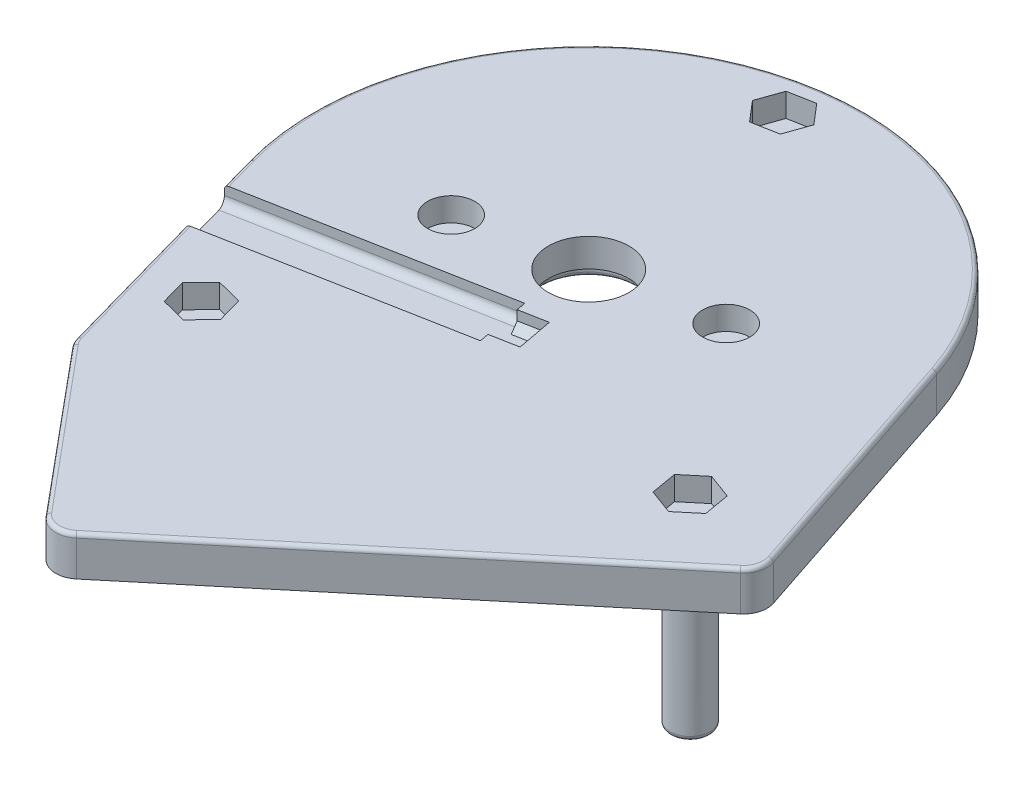
SolidWorks part; units mm, degrees
ref_plane "Front Plane" through (0, 0, 0) normal (0, 0, 1) x (1, 0, 0)
ref_plane "Top Plane" through (0, 0, 0) normal (0, 1, 0) x (1, 0, 0)
ref_plane "Right Plane" through (0, 0, 0) normal (1, 0, 0) x (0, 0, -1)
ref_plane "Plane1" through (0, 26, 0) normal (0, 1, 0) x (1, 0, 0)
sketch "Sketch1" plane through (0, 26, 0) normal (0, 1, 0) x (1, 0, 0)
  line L1 (-17.8615, -28.9506) -> (-18.7668, -25.7267)
  line L2 (-18.7668, -25.7267) -> (-22.0115, -24.8987)
  line L3 (-22.0115, -24.8987) -> (-24.3508, -27.2947)
  line L4 (-3.463, -61.6805) -> (42.6058, -23.3107)
  line L5 (43.5332, -20.0607) -> (33.2189, 11.0229)
  line L6 (-33.6967, -9.4621) -> (-25.1407, -39.932)
  line L7 (-24.5576, -41.0409) -> (-7.6881, -61.2953)
  line L8 (-3.463, -61.6805) -> (42.6058, -23.3107)
  line L9 (43.5332, -20.0607) -> (33.2189, 11.0229)
  line L10 (-33.6967, -9.4621) -> (-25.1407, -39.932)
  line L11 (-24.5576, -41.0409) -> (-7.6881, -61.2953)
  line L12 (-24.3508, -27.2947) -> (-23.4456, -30.5186)
  line L13 (-23.4456, -30.5186) -> (-20.2009, -31.3466)
  line L14 (-20.2009, -31.3466) -> (-17.8615, -28.9506)
  line L15 (31.7653, -21.5974) -> (34.3383, -19.4543)
  line L16 (34.3383, -19.4543) -> (33.7689, -16.1544)
  line L17 (33.7689, -16.1544) -> (30.6264, -14.9976)
  line L18 (30.6264, -14.9976) -> (28.0534, -17.1407)
  line L19 (28.0534, -17.1407) -> (28.6228, -20.4405)
  line L20 (28.6228, -20.4405) -> (31.7653, -21.5974)
  line L28 (0, 0) -> (-14.7176, -2.7648) construction
  line L29 (-0.9153, 4.8725) -> (0.9153, -4.8725) construction
  line L30 (-21.1062, -28.1227) -> (31.1959, -18.2975) construction
  line L52 (-7.0569, 32.1421) -> (-8.167, 28.9829)
  line L53 (-8.167, 28.9829) -> (-5.9861, 26.4418)
  line L54 (-5.9861, 26.4418) -> (-2.695, 27.0601)
  line L55 (-2.695, 27.0601) -> (-1.5849, 30.2193)
  line L56 (-1.5849, 30.2193) -> (-3.7659, 32.7604)
  line L57 (-3.7659, 32.7604) -> (-7.0569, 32.1421)
  circle A0 centre (0, 0) radius 5.125 construction
  circle A1 centre (0, 0) radius 5.125 construction
  circle A2 centre (31.1959, -18.2975) radius 3 construction
  circle A3 centre (-21.1062, -28.1227) radius 3 construction
  arc A4 (42.6058, -23.3107) -> (43.5332, -20.0607) centre (40.6859, -21.0055) ccw
  arc A5 (33.2189, 11.0229) -> (-33.6967, -9.4621) centre (0, 0) ccw
  arc A6 (-25.1407, -39.932) -> (-24.5576, -41.0409) centre (-22.2524, -39.121) ccw
  arc A7 (-7.6881, -61.2953) -> (-3.463, -61.6805) centre (-5.3829, -59.3754) ccw
  arc A8 (42.6058, -23.3107) -> (43.5332, -20.0607) centre (40.6859, -21.0055) ccw
  arc A9 (33.2189, 11.0229) -> (-33.6967, -9.4621) centre (0, 0) ccw
  arc A10 (-25.1407, -39.932) -> (-24.5576, -41.0409) centre (-22.2524, -39.121) ccw
  arc A11 (-7.6881, -61.2953) -> (-3.463, -61.6805) centre (-5.3829, -59.3754) ccw
  circle A12 centre (31.1959, -18.2975) radius 3 construction
  circle A13 centre (-21.1062, -28.1227) radius 3 construction
  circle A14 centre (0, 0) radius 5.125
  circle A15 centre (0, 0) radius 5.925
  circle A16 centre (31.1959, -18.2975) radius 1.6
  circle A17 centre (-21.1062, -28.1227) radius 1.6
  circle A18 centre (-21.1062, -28.1227) radius 2.9 construction
  circle A19 centre (31.1959, -18.2975) radius 2.9 construction
  circle A20 centre (-21.1062, -28.1227) radius 1.75
  circle A21 centre (-21.1062, -28.1227) radius 2.55
  circle A22 centre (31.1959, -18.2975) radius 1.75
  circle A23 centre (31.1959, -18.2975) radius 2.55
  circle A29 centre (-14.7176, -2.7648) radius 1.6
  circle A30 centre (-14.7176, -2.7648) radius 3
  circle A31 centre (14.7176, 2.7648) radius 1.6
  circle A32 centre (14.7176, 2.7648) radius 3
  circle A57 centre (-4.876, 29.6011) radius 1.6 construction
  circle A58 centre (-4.876, 29.6011) radius 1.6 construction
  circle A59 centre (-4.876, 29.6011) radius 1.6
  circle A60 centre (-4.876, 29.6011) radius 1.75
  circle A61 centre (-4.876, 29.6011) radius 2.55
  circle A62 centre (-4.876, 29.6011) radius 2.9 construction
  point P44 (0, 0)
  dimension "D2" = 10.25
  dimension "D3" = 11.85
  dimension "D4" = 3.2
  dimension "D6" = 3.2
  dimension "D8" = 3.2
  dimension "D9" = 6
  dimension "D11" = 3.5
  dimension "D13" = 3.5
  dimension "D15" = 3.2
  dimension "D16" = 3.5
  dimension "D5" = 5.8
  dimension "D7" = 5.8
  dimension "D10" = 29.95
  dimension "D12" = 0.8
  dimension "D14" = 0.8
  dimension "D17" = 0.8
  dimension "D18" = 5.8
  dimension "D1" = 0
extrude "Boss-Extrude7" add sketch "Sketch1" along normal blind 5 contours L11 A11 L8 A8 L9 A9 L10 A10 A30 A15 L14 L13 L12 L3 L2 L1 L20 L19 L18 L17 L16 L15 L57 L56 L55 L54 L53 L52 A32 | A30 A29 | A32 A31 | A15 A14 | L13 L14 L1 L2 L3 L12 A21 | A21 A20 | A20 A17 | L19 L20 L15 L16 L17 L18 A23 | A23 A22 | A22 A16 | L56 L57 L52 L53 L54 L55 A61 | A61 A60 | A60 A59 region at (-19.0967, 26, 30.0847) region at (1.6104, 26, 9.9024) region at (30.2255, 26, 20.9334) region at (-5.3945, 26, -32.3616) region at (-5.7574, 26, 0) region at (-22.8067, 26, 28.1227) region at (-23.5841, 26, 28.1227) region at (29.4954, 26, 18.2975) region at (28.718, 26, 18.2975) region at (-17.6327, 26, 2.7648) region at (11.8024, 26, -2.7648) region at (-6.5765, 26, -29.6011) region at (-7.3538, 26, -29.6011)
extrude "Cut-Extrude5" cut sketch "Sketch1<10>" against normal blind 3 from surface contours A30 A29 | A32 A31 | L19 L20 L15 L16 L17 L18 A23 | A23 A22 | A22 A16 | L13 L14 L1 L2 L3 L12 A21 | A21 A20 | A20 A17 | L56 L57 L52 L53 L54 L55 A61 | A61 A60 | A60 A59 region at (-19.0967, 26, 30.0847) region at (30.2255, 26, 20.9334) region at (-5.3945, 26, -32.3616) region at (-22.8067, 26, 28.1227) region at (-23.5841, 26, 28.1227) region at (29.4954, 26, 18.2975) region at (28.718, 26, 18.2975) region at (-17.6327, 26, 2.7648) region at (11.8024, 26, -2.7648) region at (-6.5765, 26, -29.6011) region at (-7.3538, 26, -29.6011) starting at face at (1.8961, 31, 26.7652)
sketch "Sketch1<10>" plane through (0, 26, 0) normal (0, 1, 0) x (1, 0, 0) same geometry as "Sketch1"
extrude "Boss-Extrude8" add sketch "Sketch1<11>" against normal blind 0.2 from surface contours A16 | A17 | A29 | A31 | A59 region at (31.1959, 26, 18.2975) region at (-21.1062, 26, 28.1227) region at (-14.7176, 26, 2.7648) region at (14.7176, 26, -2.7648) region at (-4.876, 26, -29.6011) starting at face at (-14.7176, 28, 4.3648)
sketch "Sketch1<11>" plane through (0, 26, 0) normal (0, 1, 0) x (1, 0, 0) same geometry as "Sketch1"
extrude "Cut-Extrude6" cut sketch "Sketch1<12>" along normal blind 1.4 contours A15 A14 region at (-5.7574, 26, 0)
sketch "Sketch1<12>" plane through (0, 26, 0) normal (0, 1, 0) x (1, 0, 0) same geometry as "Sketch1"
extrude "Boss-Extrude9" add sketch "Sketch1<13>" against normal blind 20.5 contours A23 A22 | A21 A20 | A61 A60 region at (-23.5841, 26, 28.1227) region at (28.718, 26, 18.2975) region at (-7.3538, 26, -29.6011)
sketch "Sketch1<13>" plane through (0, 26, 0) normal (0, 1, 0) x (1, 0, 0) same geometry as "Sketch1"
fillet "Fillet2" radius 0.6 3 edges at (-21.1062, 5.5, 30.6727) (31.1959, 5.5, 20.8475) (-4.876, 5.5, -27.8511)
fillet "Fillet3" radius 0.5 1 edges at (0, 26, 5.925)
ref_plane "Plane4" through (-0.5539, 0, -2.9484) normal (0.1846, 0, 0.9828) x (0.9828, 0, -0.1846)
ref_plane "Plane5" through (-5.0369, 0, 0.9462) normal (0.9828, 0, -0.1846) x (-0.1846, 0, -0.9828)
ref_plane "Plane6" through (0, 0, 0) normal (0.9828, 0, -0.1846) x (-0.1846, 0, -0.9828)
sketch "Sketch4" plane through (0, 0, 0) normal (0.9828, 0, -0.1846) x (-0.1846, 0, -0.9828)
  line L0 (5.125, 31) -> (-5.125, 31) construction
  line L1 (5.125, 31) -> (-5.125, 31)
  line L2 (-6.425, 26) -> (6.425, 26) construction
  line L3 (-5.125, 27.4) -> (5.125, 27.4) construction
  line L4 (-6.425, 26) -> (6.425, 26)
  line L5 (-5.125, 27.4) -> (5.125, 27.4)
  line L6 (-6.425, 26) -> (-6.425, 31)
  line L7 (-6.425, 31) -> (-5.125, 31)
  line L8 (-6.425, 31) -> (-15.1066, 31) construction
  line L9 (-13.185, 30.7) -> (-9.125, 30.7)
  line L10 (-9.125, 30.7) -> (-9.125, 29.89)
  line L11 (-9.125, 29.89) -> (-13.185, 29.89) construction
  line L12 (-13.185, 29.89) -> (-13.185, 30.7)
  line L13 (-13.185, 29.89) -> (-12.405, 29.13)
  line L14 (-12.405, 29.13) -> (-9.905, 29.13)
  line L15 (-9.905, 29.13) -> (-9.125, 29.89)
  line L16 (-11.155, 29.13) -> (-11.155, 29.89) construction
  line L17 (-13.485, 31) -> (-8.825, 31)
  line L18 (-8.825, 31) -> (-8.825, 29.7634)
  line L19 (-9.783, 28.83) -> (-8.825, 29.7634)
  line L20 (-12.527, 28.83) -> (-9.783, 28.83)
  line L21 (-13.485, 29.7634) -> (-12.527, 28.83)
  line L22 (-13.485, 29.7634) -> (-13.485, 31)
  line L23 (-12.527, 28.83) -> (-14.685, 28.83)
  line L24 (-14.685, 28.83) -> (-14.685, 31)
  line L25 (-14.685, 31) -> (-13.485, 31)
  line L26 (-9.783, 28.83) -> (-7.625, 28.83)
  line L27 (-7.625, 28.83) -> (-7.625, 31)
  line L28 (-7.625, 31) -> (-8.825, 31)
  point P16 (-11.155, 31)
  point P23 (0, 31)
  dimension "D1" = 1.57
  dimension "D2" = 0.76
  dimension "D3" = 4.06
  dimension "D4" = 2.5
  dimension "D6" = 2.4
  dimension "D7" = 1.2
  dimension "D5" = 0.3
extrude "Cut-Extrude8" cut sketch "Sketch4" against normal mid plane 3.5 contours L22 L21 L20 L19 L18 L17 L15 L14 L13 L12 L9 L10 | L14 L15 L10 L9 L12 L13 region at (2.0595, 29.9695, 10.9632) region at (2.0595, 30.9486, 10.9632)
extrude "Cut-Extrude11" cut sketch "Sketch4<5>" against normal through all from surface contours L22 L21 L20 L19 L18 L17 L15 L14 L13 L12 L9 L10 | L14 L15 L10 L9 L12 L13 | L21 | L19 region at (2.0595, 29.9695, 10.9632) region at (2.0595, 30.9486, 10.9632) region at (2.5756, 29.8016, 13.7105) region at (1.5434, 29.8016, 8.216) starting at face at (0.3396, 29.8645, 11.2863)
sketch "Sketch4<5>" plane through (0, 0, 0) normal (0.9828, 0, -0.1846) x (-0.1846, 0, -0.9828) same geometry as "Sketch4"
fillet "Fillet4" radius 1 2 edges at (-14.7777, 28.83, 17.7179) (-16.3874, 28.83, 10.8368)
sketch "Sketch6" plane through (0, 28.83, 0) normal (0, 1, 0) x (1, 0, 0)
  line L0 (0.5929, -12.6347) -> (3.5261, -9.2917) construction
  line L8 (0.0863, -9.9379) -> (-0.1275, -8.7998)
  line L9 (-30.8181, -19.7137) -> (0.8067, -13.7728)
  line L10 (-32.1913, -14.8231) -> (-30.8181, -19.7137)
  line L11 (-30.8181, -19.7137) -> (0.8067, -13.7728)
  line L12 (0.8067, -13.7728) -> (0.5929, -12.6347)
  line L13 (0.5929, -12.6347) -> (4.0327, -11.9885)
  line L14 (4.0327, -11.9885) -> (3.5261, -9.2917)
  line L15 (3.5261, -9.2917) -> (0.0863, -9.9379)
  line L16 (0.0863, -9.9379) -> (-0.1275, -8.7998)
  line L18 (-32.1913, -14.8231) -> (-30.8181, -19.7137)
  line L20 (0.8067, -13.7728) -> (0.5929, -12.6347)
  line L21 (0.5929, -12.6347) -> (4.0327, -11.9885)
  line L22 (4.0327, -11.9885) -> (3.5261, -9.2917)
  line L23 (3.5261, -9.2917) -> (0.0863, -9.9379)
  line L25 (-0.1275, -8.7998) -> (-32.1913, -14.8231)
  line L26 (-0.1275, -8.7998) -> (-32.1913, -14.8231)
  circle A0 centre (2.0595, -10.9632) radius 1
  dimension "D2" = 2
  dimension "D1" = 0
extrude "Cut-Extrude12" cut sketch "Sketch6" against normal blind 0.8 from offset 0.2 contours L0 A0 | A0 L0 region at (1.7405, 28.83, 10.6833) region at (2.3785, 28.83, 11.2432) offset against normal yes
fillet "Fillet5" radius 0.5 9 edges at (-27.8437, 31, 30.3061) (-24.9077, 31, 40.5172) (-16.1228, 31, 51.1681) (-5.6553, 31, 62.363) (19.5714, 31, 42.4956) (43.5707, 31, 21.8287) (38.3761, 31, 4.5189) (-33.0797, 31, 11.6594) (-10.2453, 31, -33.4669)
fillet "Fillet6" radius 3 3 edges at (31.1959, 26, 20.8475) (-4.876, 26, -27.0511) (-21.1062, 26, 30.6727) second distance 1.5 first distance on face at (31.1959, 6.1, 20.8475) first distance on face at (-4.876, 5.5, -27.0511) first distance on face at (-21.1062, 6.1, 30.6727)
equation "\"M3Bolt\"=3.2"
equation "\"D4@Sketch1\"=\"M3Bolt\""
equation "\"M3Nut\"=5.8"
equation "\"D5@Sketch1\"=\"M3Nut\""
equation "\"D6@Sketch1\"=\"M3Bolt\""
equation "\"D7@Sketch1\"=\"M3Nut\""
equation "\"D8@Sketch1\"=\"M3Bolt\""
equation "\"M3Socket\"=6"
equation "\"D9@Sketch1\"=\"M3Socket\""
equation "\"D13@Sketch1\"=\"D11@Sketch1\""
equation "\"D14@Sketch1\"=\"D12@Sketch1\""
equation "\"D15@Sketch1\"=\"M3Bolt\""
equation "\"D16@Sketch1\"=\"D11@Sketch1\""
equation "\"D17@Sketch1\"=\"D12@Sketch1\""
equation "\"D18@Sketch1\"=\"M3Nut\""
